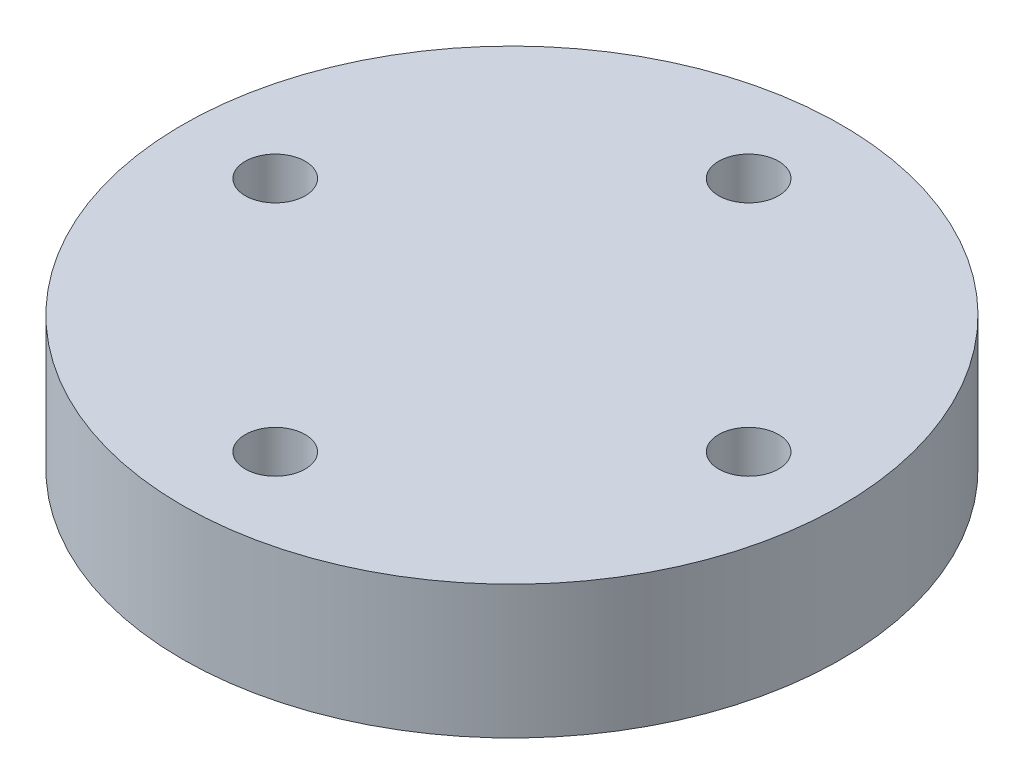
SolidWorks part; units mm, degrees
ref_plane "Front Plane" through (0, 0, 0) normal (0, 0, 1) x (1, 0, 0)
ref_plane "Top Plane" through (0, 0, 0) normal (0, 1, 0) x (1, 0, 0)
ref_plane "Right Plane" through (0, 0, 0) normal (1, 0, 0) x (0, 0, -1)
sketch "Sketch1" plane through (0, 0, 0) normal (0, 1, 0) x (1, 0, 0)
  circle A1 centre (0, 0) radius 11
  dimension "D1" = 22
extrude "Boss-Extrude1" add sketch "Sketch1" along normal blind 4.445
sketch "Sketch2" plane through (0, 4.445, 0) normal (0, 1, 0) x (1, 0, 0)
  line L0 (0, 0) -> (0, 7.9) construction
  line L1 (0, 0) -> (7.1319, 0) construction
  circle A0 centre (0, 7.9) radius 1
  point P4 (0, 6.9)
  point P5 (0, 8.9)
  point P7 (0, 8.9)
  dimension "D1" = 13.8
  dimension "D2" = 17.8
extrude "Cut-Extrude1" cut sketch "Sketch2" against normal through all
ref_axis "Axis1" through (0, 4.445, 0) along (0, -1, 0)
pattern_circular "CirPattern1" count 4 over 360 about axis through (0, 4.445, 0) along (0, -1, 0) of "Cut-Extrude1"
